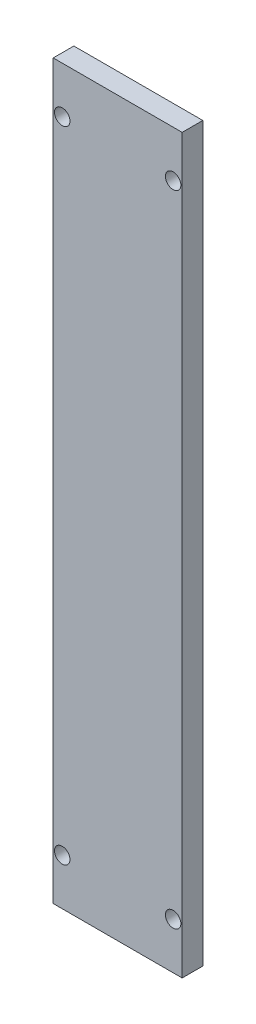
SolidWorks part; units mm, degrees
ref_plane "Front" through (0, 0, 0) normal (0, 0, 1) x (1, 0, 0)
ref_plane "Top" through (0, 0, 0) normal (0, 1, 0) x (1, 0, 0)
ref_plane "Right" through (0, 0, 0) normal (1, 0, 0) x (0, 0, -1)
sketch "Esquisse1" plane through (0, 0, 0) normal (0, 0, 1) x (1, 0, 0)
  line L1 (0, 0) -> (50, 0)
  line L2 (0, 0) -> (0, 284)
  line L3 (0, 284) -> (50, 284)
  line L4 (50, 0) -> (50, 284)
  dimension "D1" = 50
  dimension "D2" = 284
extrude "Boss.-Extru.1" add sketch "Esquisse1" along normal blind 8
sketch "Esquisse2" plane through (0, 0, 8) normal (0, 0, 1) x (1, 0, 0)
  line L0 (25, 284) -> (25, 0) construction
  line L1 (50, 284) -> (0, 284) construction
  line L2 (0, 0) -> (50, 0) construction
  line L3 (25, 142) -> (0, 142) construction
  line L4 (0, 284) -> (0, 0) construction
  circle A0 centre (3.5, 18) radius 3
  circle A1 centre (46.5, 18) radius 3
  circle A2 centre (46.5, 266) radius 3
  circle A3 centre (3.5, 266) radius 3
  dimension "D2" = 43
  dimension "D3" = 6
  dimension "D1" = 248
extrude "Enlèv. mat.-Extru.1" cut sketch "Esquisse2" against normal through all
